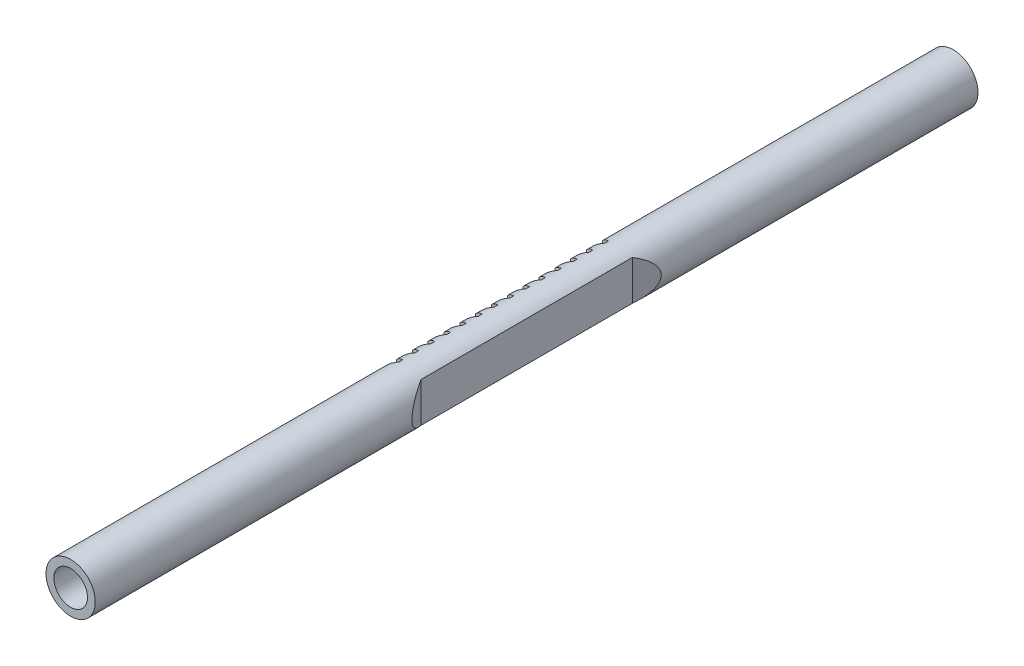
SolidWorks part; units mm, degrees
material "6061-T6 (SS)"
ref_plane "Front Plane" through (0, 0, 0) normal (0, 0, 1) x (1, 0, 0)
ref_plane "Top Plane" through (0, 0, 0) normal (0, 1, 0) x (1, 0, 0)
ref_plane "Right Plane" through (0, 0, 0) normal (1, 0, 0) x (0, 0, -1)
sketch "Sketch1" plane through (0, 0, 0) normal (0, 0, 1) x (1, 0, 0)
  circle A0 centre (0, 0) radius 10.4275
  dimension "D1" = 20.855
extrude "Boss-Extrude1" add sketch "Sketch1" along normal blind 390
sketch "Sketch2" plane through (0, 0, 0) normal (0, 0, -1) x (-1, 0, 0)
  circle A0 centre (0, 0) radius 7.112
extrude "Cut-Extrude1" cut sketch "Sketch2" against normal blind 141.75
sketch "Sketch3" plane through (0, 0, 390) normal (0, 0, 1) x (1, 0, 0)
  circle A0 centre (0, 0) radius 7.112
extrude "Cut-Extrude2" cut sketch "Sketch3" against normal blind 141.75
sketch "Sketch4" plane through (0, 0, 0) normal (0, 1, 0) x (1, 0, 0)
  line L7 (6.1894, -239.775) -> (6.1894, -150.2452)
  line L29 (-7.6275, -243.825) -> (-7.6275, -146.225)
  line L32 (10.4382, -247.7727) -> (10.4382, -142.2475)
  line L39 (-10.4275, -139.475) -> (-10.4275, -146.225) construction
  line L47 (-10.4275, -250.525) -> (-10.4275, -243.825) construction
  line L48 (-10.4275, -146.225) -> (-7.6275, -146.225)
  line L49 (-10.4275, -146.225) -> (-10.4275, -243.825)
  line L50 (-10.4275, -243.825) -> (-7.6275, -243.825)
  line L51 (10.4382, -142.2475) -> (6.1894, -150.2452)
  line L52 (6.1894, -239.775) -> (10.4382, -247.7727)
  point P15 (-7.6275, -195.025)
extrude "Cut-Extrude3" cut sketch "Sketch4" against normal blind 20 and the other way blind 20
sketch "Sketch5" plane through (0, 0, 0) normal (0, 1, 0) x (1, 0, 0)
  line L0 (-3.4275, -149.175) -> (-7.6275, -149.175) construction
  line L4 (-3.4275, -152.275) -> (-3.4275, -150.675)
  line L10 (-7.6275, -243.825) -> (-7.6275, -146.225) construction
  line L11 (-7.6275, -149.175) -> (-3.4275, -150.675)
  line L12 (-7.6275, -153.775) -> (-7.6275, -149.175)
  line L20 (-3.4275, -149.175) -> (-3.4275, -153.775) construction
  line L21 (-3.4275, -153.775) -> (-7.6275, -153.775) construction
  line L22 (-3.4275, -152.275) -> (-7.6275, -153.775)
extrude "Cut-Extrude4" cut sketch "Sketch5" against normal blind 20 and the other way blind 20
pattern_linear "LPattern1" count 14 spacing 6.7 along (0, 0, 1) of "Cut-Extrude4"
sketch "Sketch6" plane through (0, 0, 390) normal (0, 0, 1) x (1, 0, 0)
  line L1 (-12.3882, -12.5582) -> (12.3882, -12.5582)
  line L2 (-12.3882, -12.5582) -> (-12.3882, 12.5582)
  line L3 (-12.3882, 12.5582) -> (12.3882, 12.5582)
  line L4 (12.3882, -12.5582) -> (12.3882, 12.5582)
  line L5 (-12.3882, -12.5582) -> (12.3882, 12.5582) construction
  line L6 (-12.3882, 12.5582) -> (12.3882, -12.5582) construction
  point P0 (0, 0)
extrude "Cut-Extrude5" cut sketch "Sketch6" against normal blind 8.25
sketch "Sketch7" plane through (0, 0, 0) normal (0, 0, -1) x (-1, 0, 0)
  line L1 (-16.4527, -16.1861) -> (16.4527, -16.1861)
  line L2 (-16.4527, -16.1861) -> (-16.4527, 16.1861)
  line L3 (-16.4527, 16.1861) -> (16.4527, 16.1861)
  line L4 (16.4527, -16.1861) -> (16.4527, 16.1861)
  line L5 (-16.4527, -16.1861) -> (16.4527, 16.1861) construction
  line L6 (-16.4527, 16.1861) -> (16.4527, -16.1861) construction
  point P0 (0, 0)
extrude "Cut-Extrude6" cut sketch "Sketch7" against normal blind 8.25
